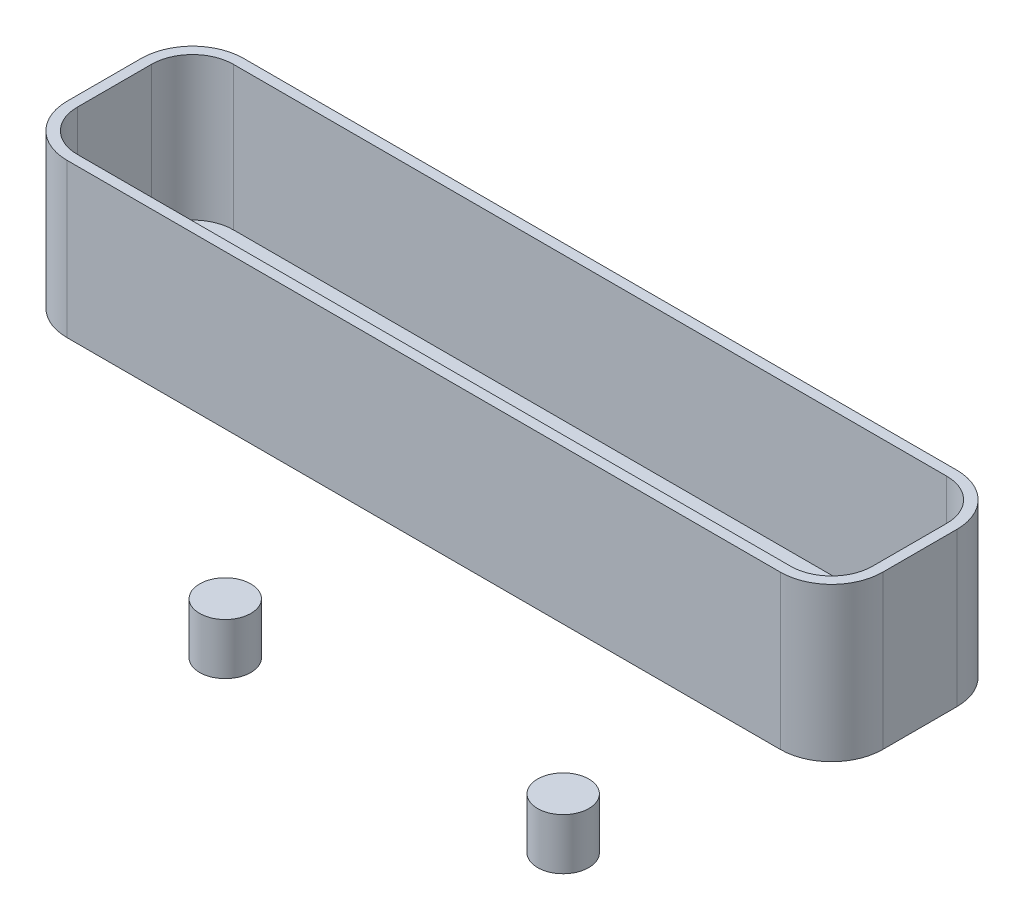
SolidWorks part; units mm, degrees
ref_plane "Front Plane" through (0, 0, 0) normal (0, 0, 1) x (1, 0, 0)
ref_plane "Top Plane" through (0, 0, 0) normal (0, 1, 0) x (1, 0, 0)
ref_plane "Right Plane" through (0, 0, 0) normal (1, 0, 0) x (0, 0, -1)
sketch "Sketch1" plane through (0, 0, 0) normal (0, -1, 0) x (1, 0, 0)
  circle A0 centre (-33, 23) radius 5
  circle A1 centre (33, 23) radius 5
  circle A2 centre (-33, -23) radius 5
  circle A3 centre (33, -23.2267) radius 5
  dimension "D1" = 10
  dimension "D2" = 10
  dimension "D3" = 10
  dimension "D4" = 10
extrude "Boss-Extrude1" add sketch "Sketch1" along normal blind 10
sketch "Sketch2" plane through (0, -10, 0) normal (0, -1, 0) x (1, 0, 0)
  line L0 (-33, 23) -> (-33, -23) construction
  line L1 (-33, 0) -> (-50.8, 0) construction
  line L2 (33, 23) -> (33, -23.2267) construction
  line L3 (33, -0.1134) -> (50.8, -0.1134) construction
  line L4 (-33, 0) -> (-0.2598, -0.0562) construction
  line L5 (0, 0) -> (0, 57.9971) construction
  line L6 (-113.3285, -24.5305) -> (-50.988, -24.9993)
  line L7 (-113.3285, -24.5305) -> (141.942, -24.5305)
  line L8 (54.5571, -0.1504) -> (33, -0.1134) construction
  line L9 (-99.7617, 17.2409) -> (79.6512, 17.2409)
  line L11 (-113.3285, -24.5305) -> (79.6512, 17.2409) construction
  line L12 (-99.7617, 17.2409) -> (141.942, -24.5305) construction
  line L13 (141.942, -24.5305) -> (64.6591, 20.6935)
  line L14 (79.6512, 17.2409) -> (58.0762, 23.8044)
  line L15 (-99.7617, 17.2409) -> (-69.4339, -16.6667)
  arc A0 (-50.988, -24.9993) -> (-69.4339, -16.6667) centre (-50.8, 0) ccw
  arc A1 (58.0762, 23.8044) -> (64.6591, 20.6935) centre (50.8, -0.1134) ccw
  dimension "D1" = 101.6
  dimension "D4" = 50
  dimension "D5" = 50
  dimension "D2" = 50.8
  dimension "D3" = 75
extrude "Boss-Extrude2" add sketch "Sketch2" along normal blind 2 rebuild error yes
sketch "Sketch3" plane through (0, 22.9291, 0) normal (0, 1, 0) x (1, 0, 0)
  line L0 (28.8512, -17.2409) -> (28.8512, -92.2409) construction
  line L1 (-21.9488, -17.2409) -> (79.6512, -17.2409) construction
  line L2 (79.6512, -92.2409) -> (-21.9488, -92.2409) construction
  line L4 (-79.6512, 17.2409) -> (79.6512, 17.2409)
  line L5 (-79.6512, 17.2409) -> (-79.6512, -17.2409)
  line L6 (-79.6512, -17.2409) -> (79.6512, -17.2409)
  line L7 (79.6512, 17.2409) -> (79.6512, -17.2409)
  line L8 (-79.6512, 17.2409) -> (79.6512, -17.2409) construction
  line L9 (-79.6512, -17.2409) -> (79.6512, 17.2409) construction
  point P6 (0, 0)
extrude "Boss-Extrude3" add sketch "Sketch3" along normal blind 30 separate body
fillet "Fillet1" radius 10 4 edges at (-79.6512, 37.9291, 17.2409) (-79.6512, 37.9291, -17.2409) (79.6512, 37.9291, 17.2409) (79.6512, 37.9291, -17.2409)
fillet "Fillet2" radius 10 rebuild error yes
fillet "Fillet3" radius 10 rebuild error yes
shell "Shell1" thickness 2 removed face at (0, 52.9291, 0)
